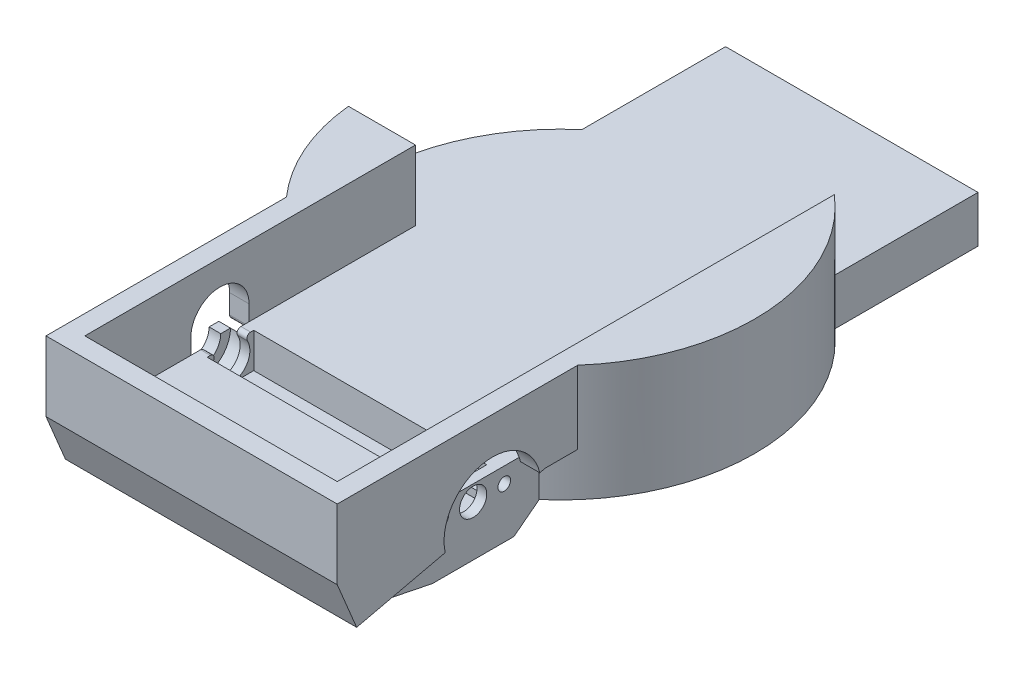
SolidWorks part; units mm, degrees
ref_plane "Front Plane" through (0, 0, 0) normal (0, 0, 1) x (1, 0, 0)
ref_plane "Top Plane" through (0, 0, 0) normal (0, 1, 0) x (1, 0, 0)
ref_plane "Right Plane" through (0, 0, 0) normal (1, 0, 0) x (0, 0, -1)
sketch "Sketch1" plane through (0, 0, 0) normal (0, 1, 0) x (1, 0, 0)
  circle A0 centre (0, 0) radius 50
  dimension "D1" = 100
extrude "Boss-Extrude1" add sketch "Sketch1" along normal blind 30
sketch "Sketch2" plane through (0, 0, 0) normal (0, -1, 0) x (1, 0, 0)
  line L0 (-2, 1.5) -> (-2, -1.5)
  circle A0 centre (0, 0) radius 4.4
  circle A1 centre (0, 0) radius 2.5
  dimension "D1" = 8.8
  dimension "D2" = 5
  dimension "D3" = 2
extrude "Boss-Extrude2" add sketch "Sketch2" along normal blind 10 contours A0 A1 | L0 A1 region at (-2.2018, 0, 0) region at (-4.2755, 0, 0)
sketch "Sketch3" plane through (0, 0, 0) normal (0, -1, 0) x (1, 0, 0)
  circle A0 centre (0, 0) radius 7.5
  circle A1 centre (0, 0) radius 4.4
  circle M2 centre (0, 0) radius 4.4
  dimension "D1" = 15
extrude "Boss-Extrude3" add sketch "Sketch3" along normal blind 2 contours A0 M2 region at (-7.2879, 0, 0)
sketch "Sketch4" plane through (0, 30, 0) normal (0, 1, 0) x (1, 0, 0)
  line L1 (32.5, 50) -> (-32.5, 50)
  line L2 (32.5, 50) -> (32.5, -50)
  line L4 (-32.5, 50) -> (-32.5, -50)
  line L5 (32.5, 50) -> (-32.5, -50) construction
  line L6 (32.5, -50) -> (-32.5, 50) construction
  line L8 (-32.5, -50) -> (32.5, -50)
  point P0 (0, 0)
  dimension "D1" = 65
  dimension "D2" = 100
extrude "Cut-Extrude1" cut sketch "Sketch4" against normal offset from surface (18 mm away) 12 up to face at (0, 0, 7.5)
ref_plane "Plane1" through (0, 12, 50) normal (0, 0, 1) x (1, 0, 0)
sketch "Sketch5" plane through (0, 12, 50) normal (0, 0, 1) x (1, 0, 0)
  line L0 (-50, -12) -> (50, -12) construction
  line L1 (-32.5, 0) -> (32.5, 0)
  line L2 (-32.5, 0) -> (-32.5, -12)
  line L3 (-32.5, -12) -> (32.5, -12)
  line L4 (32.5, 0) -> (32.5, -12)
  line L5 (-32.5, 0) -> (32.5, -12) construction
  line L6 (-32.5, -12) -> (32.5, 0) construction
  point P4 (0, -6)
extrude "Boss-Extrude4" add sketch "Sketch5" along normal blind 40 separate body
sketch "Sketch6" plane through (0, 0, 50) normal (0, 0, -1) x (-1, 0, 0)
  line L1 (-32.5, 12) -> (32.5, 12)
  line L2 (-32.5, 12) -> (-32.5, 0)
  line L3 (-32.5, 0) -> (32.5, 0)
  line L4 (32.5, 12) -> (32.5, 0)
  line L5 (-32.5, 12) -> (32.5, 0) construction
  line L6 (-32.5, 0) -> (32.5, 12) construction
  point P4 (0, 6)
extrude "Boss-Extrude5" add sketch "Sketch6" along normal up to surface up to face at (0, 21, 0)
sketch "Sketch7" plane through (0, 12, 0) normal (0, 1, 0) x (1, 0, 0)
  line L0 (0, 0) -> (0, -90) construction
  line L1 (30, -49) -> (-30, -49)
  line L2 (30, -49) -> (30, -61)
  line L3 (30, -61) -> (-30, -61)
  line L4 (-30, -49) -> (-30, -61)
  line L5 (30, -49) -> (-30, -61) construction
  line L6 (30, -61) -> (-30, -49) construction
  line L7 (32.5, -90) -> (-32.5, -90) construction
  point P0 (0, -55)
  dimension "D1" = 60
  dimension "D2" = 55
  dimension "D3" = 12
extrude "Cut-Extrude2" cut sketch "Sketch7" against normal offset from surface (9 mm away) 3 up to face at (0.25, 0, 0)
sketch "Sketch9" plane through (30, 0, 0) normal (-1, 0, 0) x (0, 0, 1)
  circle A0 centre (55, 8) radius 3.5
  dimension "D1" = 7
extrude "Cut-Extrude4" cut sketch "Sketch9" against normal up to surface (2.5 mm away) up to face at (32.5, 6, 63.9984)
sketch "Sketch11" plane through (32.5, 0, 0) normal (1, 0, 0) x (0, 0, -1)
  circle A0 centre (-55, 8) radius 8 construction
  circle A1 centre (-63, 8) radius 1.625
  circle A2 centre (-47, 8) radius 1.625
  dimension "D1" = 16
  dimension "D2" = 3.25
sketch "Sketch13" plane through (-32.5, 0, 0) normal (-1, 0, 0) x (0, 0, 1)
  line L1 (90, 0) -> (37.9967, 0) construction
  line L2 (47.5, 0) -> (62.5, 0)
  line L4 (47.5, 8) -> (39.5, 0)
  line L5 (39.5, 0) -> (47.5, 0)
  line L6 (62.5, 8) -> (70.5, 0)
  line L7 (70.5, 0) -> (62.5, 0)
  arc A0 (47.5, 8) -> (62.5, 8) centre (55, 8) ccw
  arc A1 (62.5, 8) -> (47.5, 8) centre (55, 8) cw
  line M8 (37.9967, 0) -> (90, 0)
  dimension "D1" = 15
extrude "Boss-Extrude6" add sketch "Sketch13" along normal blind 4 contours A0 M8 region at (-32.5, 0.3202, 43.5)
sketch "Sketch14" plane through (-36.5, 0, 0) normal (-1, 0, 0) x (0, 0, 1)
  line L0 (39.5, 0) -> (47.5, 8)
  line L2 (62.5, 8) -> (70.5, 0)
  line L3 (70.5, 0) -> (39.5, 0)
  line L8 (47.5, 8) -> (50, 8)
  line L10 (60, 8) -> (62.5, 8)
  arc A0 (50, 8) -> (60, 8) centre (55, 8) ccw
  arc A1 (50, 8) -> (60, 8) centre (55, 8) ccw
  point P18 (55, 13)
  arc M7 (62.5, 8) -> (47.5, 8) centre (55, 8) cw
  line M8 (47.5, 8) -> (39.5, 0)
  line M9 (39.5, 0) -> (70.5, 0)
  line M10 (70.5, 0) -> (62.5, 8)
  dimension "D1" = 10
extrude "Boss-Extrude7" add sketch "Sketch14" along normal blind 4 contours M10 M7 M8 M9 | A1 A0 M7 region at (-36.5, 3.7736, 43.7264) region at (-36.5, 7.8323, 48.75)
sketch "Sketch15" plane through (-30, 0, 0) normal (1, 0, 0) x (0, 0, -1)
  circle A0 centre (-55, 8) radius 5
  dimension "D1" = 10
extrude "Cut-Extrude7" cut sketch "Sketch15" against normal up to surface (2.5 mm away) up to face at (-32.5, 4.0625, 59.4992)
extrude "Cut-Extrude8" cut sketch "Sketch11" against normal blind 5
sketch "Sketch16" plane through (0, 0, 49) normal (0, 0, 1) x (1, 0, 0)
  line L0 (30, 7.5) -> (22, 7.5) construction
  line L1 (30, 3) -> (30, 12) construction
  line L3 (22, 10) -> (30, 10)
  line L4 (22, 10) -> (22, 5)
  line L5 (22, 5) -> (30, 5)
  line L6 (30, 10) -> (30, 5)
  line L7 (22, 10) -> (30, 5) construction
  line L8 (22, 5) -> (30, 10) construction
  point P4 (26, 7.5)
  dimension "D1" = 8
  dimension "D2" = 5
extrude "Cut-Extrude9" cut sketch "Sketch16" against normal blind 5 and the other way blind 17
sketch "Sketch17" plane through (0, 0, 0) normal (0, -1, 0) x (1, 0, 0)
  line L0 (-40.5, 65.5) -> (32.5, 65.5)
  line L1 (-40.5, 39.5) -> (-40.5, 70.5) construction
  line L2 (32.5, 37.9967) -> (32.5, 90) construction
  line L3 (-40.5, 44.5) -> (32.5, 44.5)
  line L4 (-40.5, 65.5) -> (-40.5, 44.5)
  line L5 (32.5, 65.5) -> (32.5, 44.5)
  line L6 (-40.5, 70.5) -> (-32.5, 70.5) construction
  line L7 (-40.5, 39.5) -> (-32.5, 39.5) construction
  point P10 (-36.5, 70.5)
  dimension "D1" = 5
  dimension "D2" = 5
extrude "Boss-Extrude8" add sketch "Sketch17" along normal blind 5
sketch "Sketch18" plane through (32.5, 0, 0) normal (1, 0, 0) x (0, 0, -1)
  line L0 (-65.5, -5) -> (-90, 0)
  line L1 (-90, 0) -> (-65.5, 0)
  line L2 (-65.5, 0) -> (-65.5, -5)
  line L3 (-44.5, -5) -> (-44.5, 0)
  line L4 (-44.5, 0) -> (-37.9967, 0)
  line L5 (-37.9967, 0) -> (-44.5, -5)
extrude "Boss-Extrude9" add sketch "Sketch18" against normal up to surface (65 mm away) up to face at (-32.5, 4.75, 58.5993)
sketch "Sketch19" plane through (-40.5, 0, 0) normal (-1, 0, 0) x (0, 0, 1)
  line L0 (65.5, -5) -> (70.5, 0)
  line L1 (70.5, 0) -> (65.5, 0)
  line L2 (65.5, 0) -> (65.5, -5)
  line L3 (44.5, -5) -> (39.5, 0)
  line L4 (39.5, 0) -> (44.5, 0)
  line L5 (44.5, 0) -> (44.5, -5)
extrude "Boss-Extrude10" add sketch "Sketch19" against normal up to surface (8 mm away) up to face at (-32.5, 2.6786, 57.571)
fillet "Fillet2" radius 1 2 edges at (-31.25, 12, 58) (-31.25, 12, 52)
sketch "Sketch20" plane through (0, 12, 0) normal (0, 1, 0) x (1, 0, 0)
  line L1 (-32.5, -90) -> (32.5, -90)
  line L2 (-32.5, -90) -> (-32.5, -95)
  line L3 (-32.5, -95) -> (32.5, -95)
  line L4 (32.5, -90) -> (32.5, -95)
  line L5 (-32.5, -90) -> (32.5, -95) construction
  line L6 (-32.5, -95) -> (32.5, -90) construction
  point P4 (0, -92.5)
  dimension "D1" = 5
extrude "Boss-Extrude11" add sketch "Sketch20" along normal up to surface (18 mm away) separate body up to face at (-41.25, 30, 0)
sketch "Sketch22" plane through (32.5, 0, 0) normal (1, 0, 0) x (0, 0, -1)
  line L0 (-95, 12) -> (-90, 0)
  line L1 (-90, 0) -> (-90, 12)
  line L2 (-90, 12) -> (-95, 12)
extrude "Boss-Extrude12" add sketch "Sketch22" against normal up to surface (65 mm away) up to face at (-32.5, 21, 92.5)
ref_plane "Plane2" through (0, 12, -50) normal (0, 0, -1) x (-1, 0, 0)
sketch "Sketch23" plane through (0, 12, -50) normal (0, 0, -1) x (-1, 0, 0)
  line L1 (-32.5, 0) -> (32.5, 0)
  line L2 (-32.5, 0) -> (-32.5, -12)
  line L3 (-32.5, -12) -> (32.5, -12)
  line L4 (32.5, 0) -> (32.5, -12)
  line L5 (-32.5, 0) -> (32.5, -12) construction
  line L6 (-32.5, -12) -> (32.5, 0) construction
  point P4 (0, -6)
extrude "Boss-Extrude13" add sketch "Sketch23" along normal blind 25 separate body
sketch "Sketch24" plane through (0, 0, -50) normal (0, 0, 1) x (1, 0, 0)
  line L1 (-32.5, 12) -> (32.5, 12)
  line L2 (-32.5, 12) -> (-32.5, 0)
  line L3 (-32.5, 0) -> (32.5, 0)
  line L4 (32.5, 12) -> (32.5, 0)
  line L5 (-32.5, 12) -> (32.5, 0) construction
  line L6 (-32.5, 0) -> (32.5, 12) construction
  point P4 (0, 6)
extrude "Boss-Extrude14" add sketch "Sketch24" along normal up to surface (12.0033 mm away) up to face at (0, 16.8, -2.4007)
sketch "Sketch25" plane through (32.5, 0, 0) normal (1, 0, 0) x (0, 0, -1)
  line L0 (-95, 30) -> (-95, 12)
  line L1 (-95, 12) -> (-90, 0)
  line L2 (-95, 30) -> (-41.3633, 30)
  line L9 (-41.3633, 11.2231) -> (-90, 0)
  line L10 (-41.3633, 30) -> (-41.3633, 11.2231)
extrude "Boss-Extrude19" add sketch "Sketch25" along normal blind 5
sketch "Sketch26" plane through (0, 0, 41.3633) normal (0, 0, -1) x (-1, 0, 0)
  line L2 (-37.5, 30) -> (-32.5, 30)
  line L3 (-37.5, 30) -> (-37.5, 11.2231)
  line L4 (-37.5, 11.2231) -> (-32.5, 11.2231)
  line L5 (-32.5, 30) -> (-32.5, 11.2231)
  line L6 (-37.5, 30) -> (-32.5, 11.2231) construction
  line L7 (-37.5, 11.2231) -> (-32.5, 30) construction
  point P6 (-35, 20.6116)
extrude "Boss-Extrude20" add sketch "Sketch26" along normal up to surface (3.3666 mm away) up to face at (38.3333, 14, 0)
sketch "Sketch27" plane through (32.5, 0, 0) normal (1, 0, 0) x (0, 0, -1)
  circle A0 centre (-55, 8) radius 12.5
  dimension "D1" = 25
extrude "Cut-Extrude10" cut sketch "Sketch27" along normal up to surface (5 mm away) up to face at (37.5, 15.741, 64.5845)
sketch "Sketch28" plane through (-32.5, 0, 0) normal (-1, 0, 0) x (0, 0, 1)
  line L0 (95, 30) -> (43.629, 30)
  line L2 (43.629, 10.7003) -> (90, 0)
  line L3 (90, 0) -> (95, 12)
  line L4 (95, 12) -> (95, 30)
  line L6 (43.629, 30) -> (43.629, 10.7003)
extrude "Boss-Extrude23" add sketch "Sketch28" along normal blind 5
sketch "Sketch29" plane through (0, 0, 43.629) normal (0, 0, -1) x (-1, 0, 0)
  line L1 (32.5, 30) -> (37.5, 30)
  line L2 (32.5, 30) -> (32.5, 10.7003)
  line L3 (32.5, 10.7003) -> (37.5, 10.7003)
  line L4 (37.5, 30) -> (37.5, 10.7003)
  line L5 (32.5, 30) -> (37.5, 10.7003) construction
  line L6 (32.5, 10.7003) -> (37.5, 30) construction
  point P4 (35, 20.3502)
extrude "Boss-Extrude24" add sketch "Sketch29" along normal up to surface (10.5571 mm away) up to face at (-38.3333, 14, 0)
sketch "Sketch30" plane through (-32.5, 0, 0) normal (-1, 0, 0) x (0, 0, 1)
  circle A0 centre (55, 8) radius 7.5
  dimension "D1" = 15
extrude "Cut-Extrude11" cut sketch "Sketch30" along normal up to surface (5 mm away) up to face at (-37.5, 12.2196, 63.6839)
sketch "Sketch32" plane through (-37.5, 0, 0) normal (-1, 0, 0) x (0, 0, 1)
  line L0 (47.7091, 15.9973) -> (62.7091, 15.9973) construction
  line L5 (55.2091, 9.7588) -> (55.2091, 15.9973) construction
  line L6 (47.7091, 9.7588) -> (47.7091, 15.9973)
  line L7 (62.7091, 9.7588) -> (62.7091, 15.9973)
  line L8 (47.7091, 9.7588) -> (62.7091, 9.7588)
  line L9 (43.629, 10.7003) -> (47.7091, 9.7588) construction
  arc A4 (62.7091, 15.9973) -> (47.7091, 15.9973) centre (55.2091, 15.9973) ccw
  point P0 (62.7091, 9.7588)
  point P2 (55, 8)
  point P3 (55.2091, 15.9973)
  arc M6 (47.7091, 9.7588) -> (62.5, 8) centre (55, 8) cw
  dimension "D1" = 7.5
  dimension "D2" = 8
extrude "Cut-Extrude14" cut sketch "Sketch32" against normal up to surface (5 mm away) contours L0 A4 | L8 L5 M6 | L5 L8 M6 region at (-37.5, 12.1526, 55) region at (-37.5, 17.9066, 55.3178) up to face at (-32.5, 6.6918, 48.5692)
fillet "Fillet4" radius 1 2 edges at (-35, 9.7588, 62.2909) (-35, 9.7588, 47.7091)
sketch "Sketch35" plane through (-32.5, 0, 0) normal (1, 0, 0) x (0, 0, -1)
  line L0 (-47.7091, 12) -> (37.9967, 12) construction
  line L1 (37.9967, 30) -> (-4.8562, 30)
  line L2 (37.9967, 30) -> (37.9967, 12)
  line L3 (37.9967, 12) -> (-4.8562, 12)
  line L4 (-4.8562, 30) -> (-4.8562, 12)
  line L5 (37.9967, 30) -> (-4.8562, 12) construction
  line L6 (37.9967, 12) -> (-4.8562, 30) construction
  point P4 (16.5702, 21)
extrude "Cut-Extrude15" cut sketch "Sketch35" against normal through all
